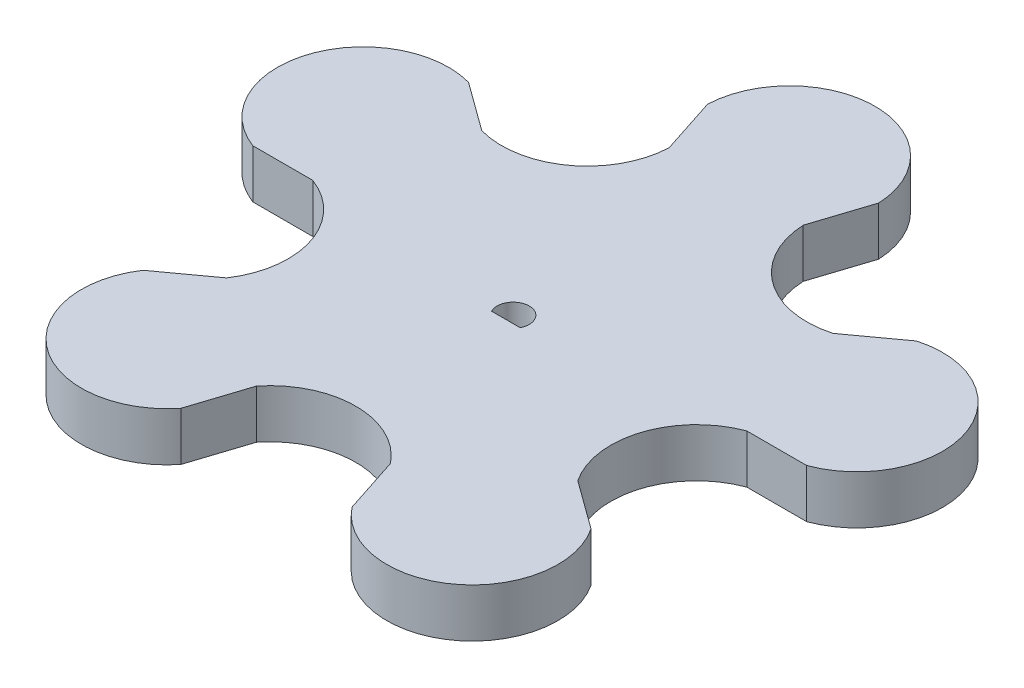
SolidWorks part; units mm, degrees
ref_plane "Front Plane" through (0, 0, 0) normal (0, 0, 1) x (1, 0, 0)
ref_plane "Top Plane" through (0, 0, 0) normal (0, 1, 0) x (1, 0, 0)
ref_plane "Right Plane" through (0, 0, 0) normal (1, 0, 0) x (0, 0, -1)
sketch "Sketch2" plane through (0, 0, 0) normal (0, 1, 0) x (1, 0, 0)
  line L0 (0, 0) -> (0, 16.9342) construction
  line L1 (-5.5828, 34.124) -> (-4.3753, 30.4076)
  line L2 (-4.3753, 30.4076) -> (-4.3565, 30.3846)
  line L3 (-14.616, 6.3226) -> (-11.4547, 8.6195)
  line L4 (-18.0664, 16.9418) -> (-14.1588, 16.9418)
  line L5 (-14.616, 27.561) -> (-11.4547, 25.2641)
  line L6 (5.5828, 34.124) -> (4.3753, 30.4076)
  line L7 (14.616, 27.561) -> (11.4547, 25.2641)
  line L8 (18.0664, 16.9418) -> (14.1588, 16.9418)
  line L9 (14.1588, 16.9418) -> (14.1782, 17.0613)
  line L10 (14.616, 6.3226) -> (11.4547, 8.6195)
  line L11 (11.4547, 8.6195) -> (11.6097, 8.7137)
  line L12 (5.5828, -0.2404) -> (4.3753, 3.476)
  line L13 (-5.5828, -0.2404) -> (-4.3753, 3.476)
  circle A0 centre (0, 16.9342) radius 16.9442 construction
  arc A1 (-14.616, 6.3226) -> (-5.5828, -0.2404) centre (-9.9581, 3.2356) ccw
  arc A3 (-14.616, 27.561) -> (-18.0664, 16.9418) centre (-16.1126, 22.1771) ccw
  arc A7 (18.0664, 16.9418) -> (14.616, 27.561) centre (16.1126, 22.1771) ccw
  arc A9 (5.5828, -0.2404) -> (14.616, 6.3226) centre (9.9581, 3.2356) ccw
  arc A10 (-11.4547, 25.2641) -> (-4.3753, 30.4076) centre (-9.9581, 30.648) ccw
  arc A12 (-11.4547, 8.6195) -> (-14.1588, 16.9418) centre (-16.1126, 11.7065) ccw
  arc A14 (4.3753, 3.476) -> (-4.3753, 3.476) centre (0, 0) ccw
  arc A16 (14.1588, 16.9418) -> (11.4547, 8.6195) centre (16.1126, 11.7065) ccw
  arc A18 (5.5828, 34.124) -> (-5.5828, 34.124) centre (0, 33.8836) ccw
  arc A19 (4.3753, 30.4076) -> (11.4547, 25.2641) centre (9.9581, 30.648) ccw
  point P25 (0, 16.9418)
extrude "Boss-Extrude1" add sketch "Sketch2" along normal blind 3.175 contours A19 L6 A18 L1 A10 L5 A3 L4 A12 L3 A1 L13 A14 L12 A9 L10 A16 L8 A7 L7 region at (0, 0, -16.9418)
sketch "Sketch3" plane through (0, 3.175, 0) normal (0, 1, 0) x (1, 0, 0)
  line L0 (0, 5.588) -> (10.7981, 13.4333) construction
  line L1 (10.9624, 13.8748) -> (6.6736, 26.1272) construction
  line L2 (6.6736, 26.1272) -> (-6.6736, 26.1272) construction
  line L3 (-6.6736, 26.1272) -> (-10.7981, 13.4333) construction
  line L4 (-10.7981, 13.4333) -> (0, 5.588) construction
  line L5 (0, 26.1272) -> (0, 5.588) construction
  line L6 (0, 16.9054) -> (0, 15.3814) construction
  line L7 (-0.9333, 15.3814) -> (0.9333, 15.3814)
  arc A0 (0.9333, 15.3814) -> (-0.9333, 15.3814) centre (0, 15.8576) ccw
  arc A15 (4.3753, 3.476) -> (-4.3753, 3.476) centre (0, 0) ccw construction
  arc A16 (14.1588, 16.9418) -> (11.4547, 8.6195) centre (16.1126, 11.7065) ccw construction
  arc A17 (4.3753, 30.4076) -> (11.4547, 25.2641) centre (9.9581, 30.648) ccw construction
  arc A18 (-11.4547, 25.2641) -> (-4.3753, 30.4076) centre (-9.9581, 30.648) ccw construction
  arc A19 (-11.4547, 8.6195) -> (-14.1588, 16.9418) centre (-16.1126, 11.7065) ccw construction
extrude "Cut-Extrude1" cut sketch "Sketch3" against normal through all
